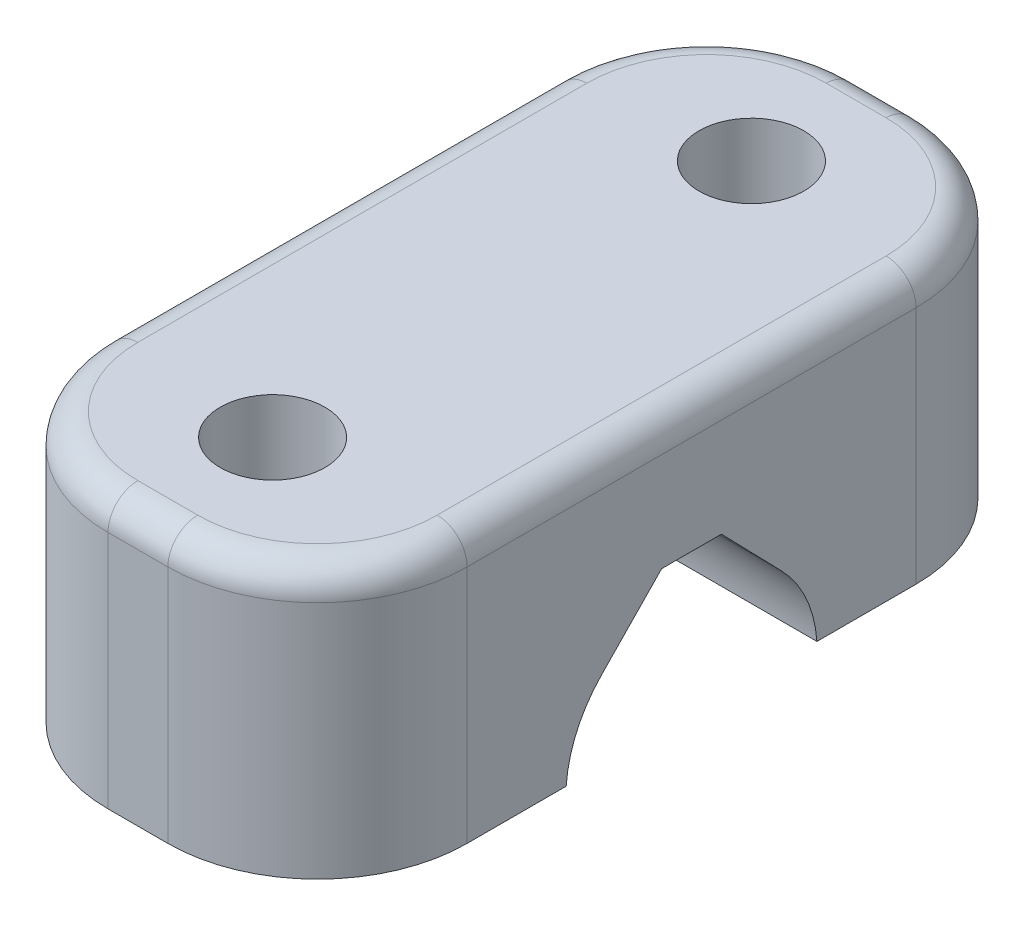
SolidWorks part; units mm, degrees
ref_plane "Alzado" through (0, 0, 0) normal (0, 0, 1) x (1, 0, 0)
ref_plane "Planta" through (0, 0, 0) normal (0, 1, 0) x (1, 0, 0)
ref_plane "Vista lateral" through (0, 0, 0) normal (1, 0, 0) x (0, 0, -1)
sketch "Croquis1" plane through (0, 0, 0) normal (0, 1, 0) x (1, 0, 0)
  line L0 (0, -55) -> (0, 55) construction
  line L1 (0, 12.5) -> (12, 12.5)
  line L2 (0, 12.5) -> (0, -12.5)
  line L3 (0, -12.5) -> (12, -12.5)
  line L4 (12, 12.5) -> (12, -12.5)
  line L5 (-8.7591, 0) -> (38.4995, 0) construction
  line L6 (-55, 0) -> (55, 0) construction
  dimension "D1" = 25
  dimension "D2" = 12
extrude "Saliente-Extruir1" add sketch "Croquis1" along normal blind 9
sketch "Croquis3" plane through (0, 0, 0) normal (1, 0, 0) x (0, 0, -1)
  line L0 (-3.0138, 2.6252) -> (-1, 4.7)
  line L1 (-1, 4.7) -> (1, 4.7)
  line L2 (1, 4.7) -> (3.0138, 2.6252)
  line L3 (0, 9.5392) -> (0, -5.3638) construction
  line L4 (0, 4.95) -> (0, -4.95) construction
  line L5 (6.6, 0) -> (-6.6, 0) construction
  arc A0 (-3.0138, 2.6252) -> (3.0138, 2.6252) centre (0, -0.3) ccw
  dimension "D1" = 8.4
  dimension "D2" = 2
  dimension "D3" = 5
  dimension "D4" = 0.3
extrude "Cortar-Extruir1" cut sketch "Croquis3" along normal through all
sketch "Croquis4" plane through (0, 0, 0) normal (0, -1, 0) x (1, 0, 0)
  line L0 (-0.9259, 0) -> (32.8144, 0) construction
  line L1 (4.95, 0) -> (-4.95, 0) construction
  line L2 (12, 12.5) -> (12, 4.1893) construction
  circle A0 centre (6, 8) radius 1.75
  circle A3 centre (6, -8) radius 1.75
  dimension "D3" = 3.5
  dimension "D1" = 16
  dimension "D2" = 6
extrude "Cortar-Extruir2" cut sketch "Croquis4" against normal through all
fillet "Redondeo1" radius 5 4 edges at (0, 4.5, -12.5) (12, 4.5, -12.5) (12, 4.5, 12.5) (0, 4.5, 12.5)
fillet "Redondeo2" radius 1 8 edges at (10.5355, 9, -11.0355) (12, 9, 0) (10.5355, 9, 11.0355) (6, 9, 12.5) (1.4645, 9, 11.0355) (0, 9, 0) (1.4645, 9, -11.0355) (6, 9, -12.5)
